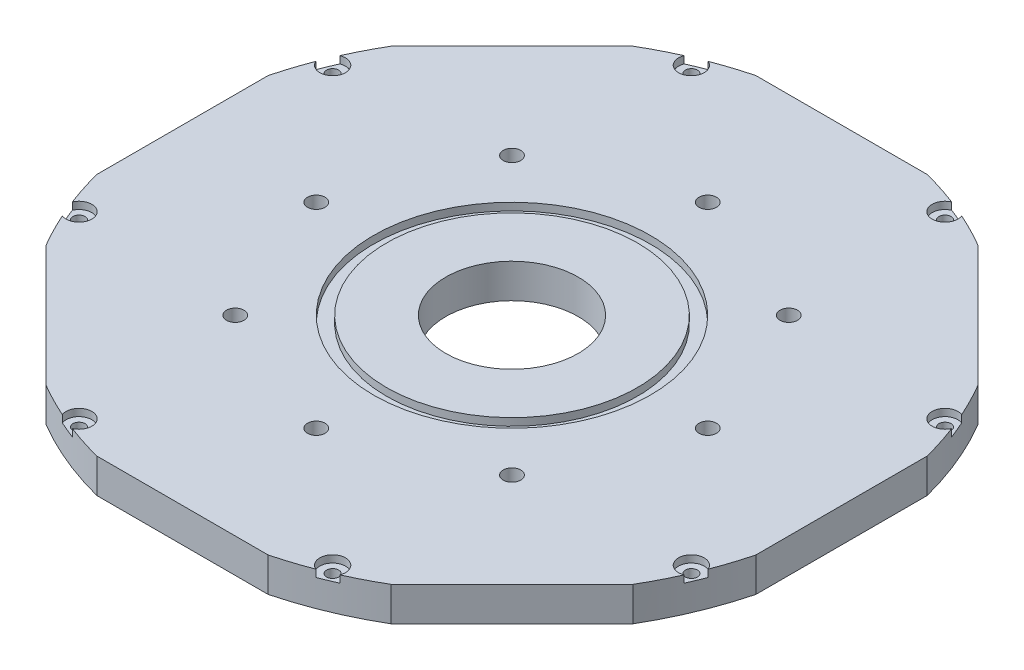
SolidWorks part; units mm, degrees
other "Markup1"
sketch "Sketch46" plane through (-122.3, 0, 122.3) normal (-0.1263, -0.9546, 0.2699) x (-0.172, -0.2469, -0.9537)
material "6061-T6 (SS)"
ref_plane "Front Plane" through (0, 0, 0) normal (0, 0, 1) x (1, 0, 0)
ref_plane "Top Plane" through (0, 0, 0) normal (0, 1, 0) x (1, 0, 0)
ref_plane "Right Plane" through (0, 0, 0) normal (1, 0, 0) x (0, 0, -1)
sketch "Sketch1" plane through (0, 0, 0) normal (0, 1, 0) x (1, 0, 0)
  line L1 (-50.6583, 122.3) -> (-122.3, 50.6583)
  line L2 (-122.3, 50.6583) -> (-122.3, -50.6583)
  line L3 (-122.3, -50.6583) -> (-50.6583, -122.3)
  line L4 (-50.6583, -122.3) -> (50.6583, -122.3)
  line L5 (50.6583, -122.3) -> (122.3, -50.6583)
  line L6 (122.3, -50.6583) -> (122.3, 50.6583)
  line L7 (122.3, 50.6583) -> (50.6583, 122.3)
  line L8 (50.6583, 122.3) -> (-50.6583, 122.3)
  circle A0 centre (0, 0) radius 122.3 construction
  circle A1 centre (0, 0) radius 126.365
  dimension "D2" = 252.73
  dimension "D1" = 244.6
extrude "Boss-Extrude1" add sketch "Sketch1" along normal blind 12.7 contours L4 A1 L5 L6 L7 L8 L1 L2 L3 region at (0, 0, 0)
sketch "Sketch3" plane through (0, 12.7, 0) normal (0, 1, 0) x (1, 0, 0)
  circle A0 centre (0, 0) radius 24.5745
  dimension "D1" = 49.149
extrude "Cut-Extrude1" cut sketch "Sketch3" against normal through all contours A0
sketch "Sketch5" plane through (0, 12.7, 0) normal (0, 1, 0) x (1, 0, 0)
  circle A0 centre (0, 0) radius 46.5455
  circle A1 centre (0, 0) radius 51.3715
  dimension "D1" = 93.091
  dimension "D2" = 102.743
extrude "Cut-Extrude2" cut sketch "Sketch5" against normal blind 2.794
sketch "Sketch19" plane through (0, 12.7, 0) normal (0, 1, 0) x (1, 0, 0)
  line L5 (-63.9978, 108.9605) -> (-31.7934, 122.3) construction
  line L6 (-47.8956, 115.6303) -> (-43.6974, 105.4949) construction
  circle A4 centre (0, 0) radius 122.9995
  circle A5 centre (-47.0699, 113.6367) radius 2.2479
  dimension "D1" = 4.4958
  dimension "D3" = 245.999
sketch "Sketch21" plane through (0, 12.7, 0) normal (0, 1, 0) x (1, 0, 0)
  point P0 (-72.644, 0)
  dimension "D1" = 72.644
hole_wizard "5/16-18 Tapped Hole1" positions "Sketch22" profile "Sketch23" tap size "5/16-18" standard "ANSI Inch"
sketch "Sketch22" plane through (0, 12.7, 0) normal (0, 1, 0) x (1, 0, 0)
  point P0 (-72.644, 0)
sketch "Sketch23" plane through (-72.644, 12.7, 0) normal (1, 0, 0) x (0, 0, 1)
  line L0 (0, 0) -> (0, 8.3111)
  line L1 (0, 8.3111) -> (3.2639, 6.35)
  line L2 (3.2639, 6.35) -> (3.2639, 0)
  line L5 (3.2639, 0) -> (0, 0)
  line L10 (0, 8.3111) -> (-3.2639, 6.35) construction
  line L11 (0, -6.35) -> (0, 107.95) construction
  dimension "Tap Drill Dia." = 6.5278
  dimension "Tap Drill Depth" = 6.35
  dimension "Drill Angle" = 118
cosmetic thread "Hole Thread2" parameters "D1"=6.35, "D2"=7.9375
sketch "Sketch33" [suppressed] plane through (0, 19.05, 0) normal (0, 1, 0) x (1, 0, 0)
  circle A0 centre (-71.374, 0) radius 3.9687
  dimension "D1" = 7.9375
sketch "Sketch37" plane through (0, 0, 0) normal (0, -1, 0) x (1, 0, 0)
  circle A0 centre (0, 0) radius 119.0625
  circle A1 centre (0, 0) radius 115.2525
  dimension "D1" = 238.125
  dimension "D2" = 230.505
extrude "Cut-Extrude7" [suppressed] cut sketch "Sketch37" against normal blind 2.667
pattern_circular "CirPattern4" count 8 over 360 about axis through (0, 0, 0) along (0, 1, 0) of "5/16-18 Tapped Hole1" reverse direction yes
cosmetic thread "Hole Thread3" parameters "D1"=6.35, "D2"=7.9375
cosmetic thread "Hole Thread4" parameters "D1"=6.35, "D2"=7.9375
cosmetic thread "Hole Thread5" parameters "D1"=6.35, "D2"=7.9375
cosmetic thread "Hole Thread6" parameters "D1"=6.35, "D2"=7.9375
cosmetic thread "Hole Thread7" parameters "D1"=6.35, "D2"=7.9375
cosmetic thread "Hole Thread8" parameters "D1"=6.35, "D2"=7.9375
cosmetic thread "Hole Thread9" parameters "D1"=6.35, "D2"=7.9375
hole_wizard "CBORE for #8 Binding Head Machine Screw2" positions "Sketch47" profile "Sketch49" counterbore size "#8" standard "ANSI Inch" end condition through all
sketch "Sketch47" plane through (0, 12.7, 0) normal (0, 1, 0) x (1, 0, 0)
  point P0 (-47.0699, 113.6367)
sketch "Sketch49" plane through (-47.0699, 12.7, -113.6367) normal (1, 0, 0) x (0, 0, 1)
  line L0 (0, 0) -> (0, 12.7)
  line L1 (0, 12.7) -> (2.2479, 12.7)
  line L3 (2.2479, 12.7) -> (2.2479, 2.667)
  line L4 (2.2479, 2.667) -> (4.7625, 2.667)
  line L5 (4.7625, 2.667) -> (4.7625, 0)
  line L7 (4.7625, 0) -> (0, 0)
  line L11 (0, -6.35) -> (0, 107.95) construction
  dimension "Thru Hole Dia." = 4.4958
  dimension "Thru Hole Depth" = 12.7
  dimension "C'Bore Dia." = 9.525
  dimension "C'Bore Depth" = 2.667
pattern_circular "CirPattern5" count 8 over 360 about axis through (0, 0, 0) along (0, 1, 0) of "CBORE for #8 Binding Head Machine Screw2"
